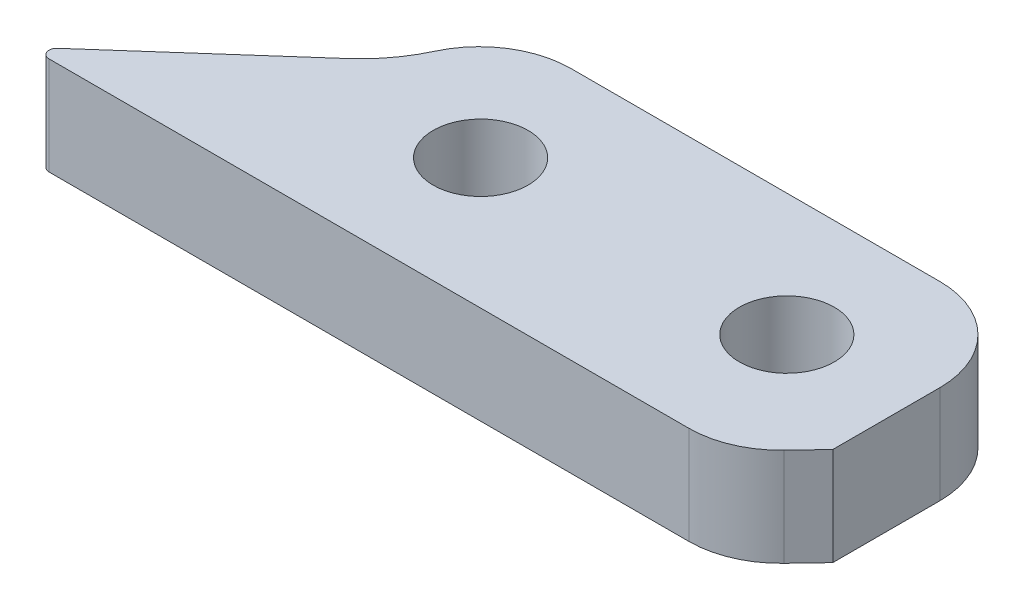
SolidWorks part; units mm, degrees
material "Titanium Ti-8Mn, Annealed"
ref_plane "Front Plane" through (0, 0, 0) normal (0, 0, 1) x (1, 0, 0)
ref_plane "Top Plane" through (0, 0, 0) normal (0, 1, 0) x (1, 0, 0)
ref_plane "Right Plane" through (0, 0, 0) normal (1, 0, 0) x (0, 0, -1)
sketch "Sketch1" plane through (0, 0, 0) normal (0, 1, 0) x (1, 0, 0)
  line L5 (36, -13) -> (36, 0)
  line L6 (36, 0) -> (0, 0)
  line L8 (36, -13) -> (32.6676, -16.5)
  line L9 (32.6676, -16.5) -> (-1.4555, -16.5)
  line L10 (0, 0) -> (0, -5)
  line L11 (0, -5) -> (-13, -16.5)
  line L12 (-13, -16.5) -> (-1.4555, -16.5)
  circle A0 centre (28, -8) radius 3.1
  circle A1 centre (8, -8) radius 3.1
  dimension "D8" = 6.2
  dimension "D9" = 6.2
  dimension "D1" = 13
  dimension "D2" = 36
  dimension "D3" = 8
  dimension "D4" = 13
  dimension "D5" = 5
  dimension "D6" = 8.5
  dimension "D10" = 20
  dimension "D11" = 8
extrude "Boss-Extrude1" add sketch "Sketch1" along normal blind 6.4
fillet "Fillet1" radius 6 3 edges at (32.6676, 3.2, 16.5) (36, 3.2, 0) (0, 3.2, 0)
fillet "Fillet2" radius 10 1 edges at (0, 3.2, 5)
fillet "Fillet3" radius 0.5 1 edges at (-13, 3.2, 16.5)
